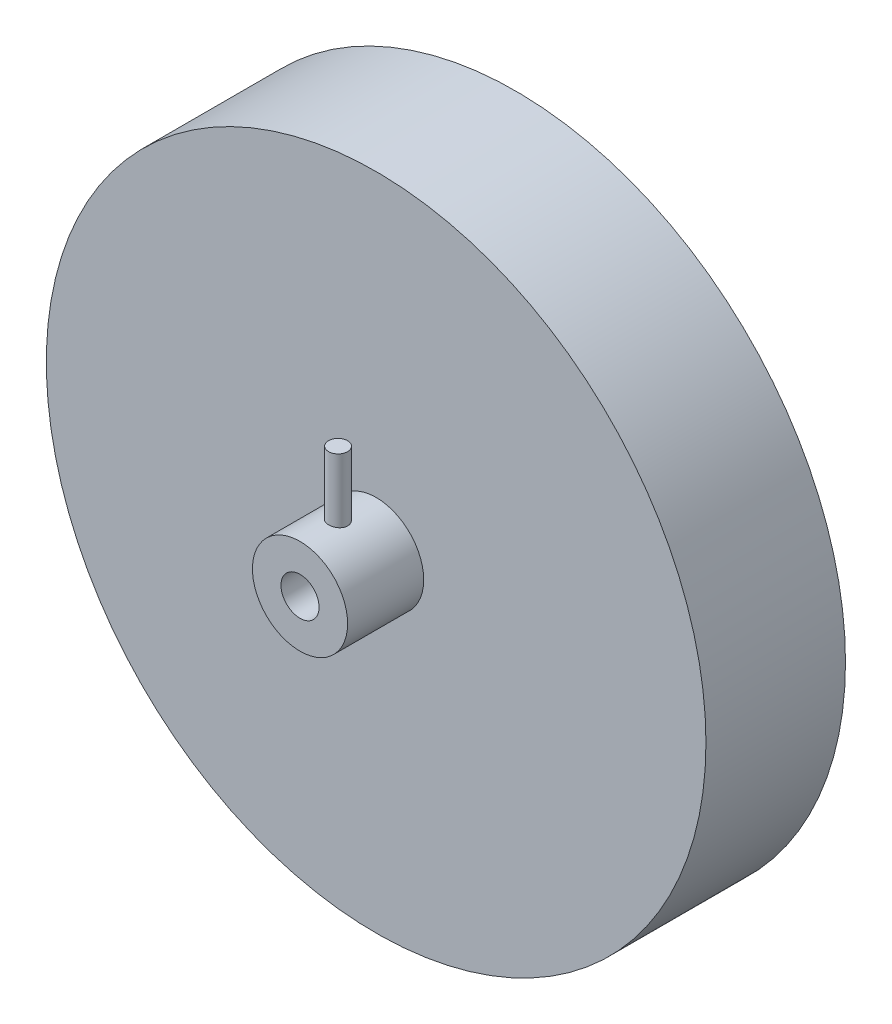
SolidWorks part; units mm, degrees
ref_plane "Front Plane" through (0, 0, 0) normal (0, 0, 1) x (1, 0, 0)
ref_plane "Top Plane" through (0, 0, 0) normal (0, 1, 0) x (1, 0, 0)
ref_plane "Right Plane" through (0, 0, 0) normal (1, 0, 0) x (0, 0, -1)
sketch "Sketch1" plane through (0, 0, 0) normal (0, 0, 1) x (1, 0, 0)
  circle A0 centre (0, 0) radius 52
  dimension "D1" = 104
extrude "Boss-Extrude1" add sketch "Sketch1" along normal mid plane 22
sketch "Sketch2" plane through (0, 0, 11) normal (0, 0, 1) x (1, 0, 0)
  circle A0 centre (0, 0) radius 7.5
  dimension "D1" = 15
extrude "Boss-Extrude2" add sketch "Sketch2" along normal blind 12
sketch "Sketch3" plane through (0, 0, 0) normal (0, 1, 0) x (1, 0, 0)
  line L0 (0, 11) -> (0, -23) construction
  line L2 (52, 11) -> (-52, 11) construction
  line L3 (-7.5, -23) -> (7.5, -23) construction
  circle A0 centre (0, -17) radius 1.5
  point P2 (0, -23)
  point P9 (0, -15.0687)
  dimension "D1" = 3
  dimension "D2" = 6
extrude "Boss-Extrude3" add sketch "Sketch3" along normal blind 17.5
sketch "Sketch4" plane through (0, 0, 23) normal (0, 0, -1) x (-1, 0, 0)
  circle A0 centre (0, 0) radius 3
  dimension "D1" = 6
extrude "Cut-Extrude3" cut sketch "Sketch4" along normal blind 12
